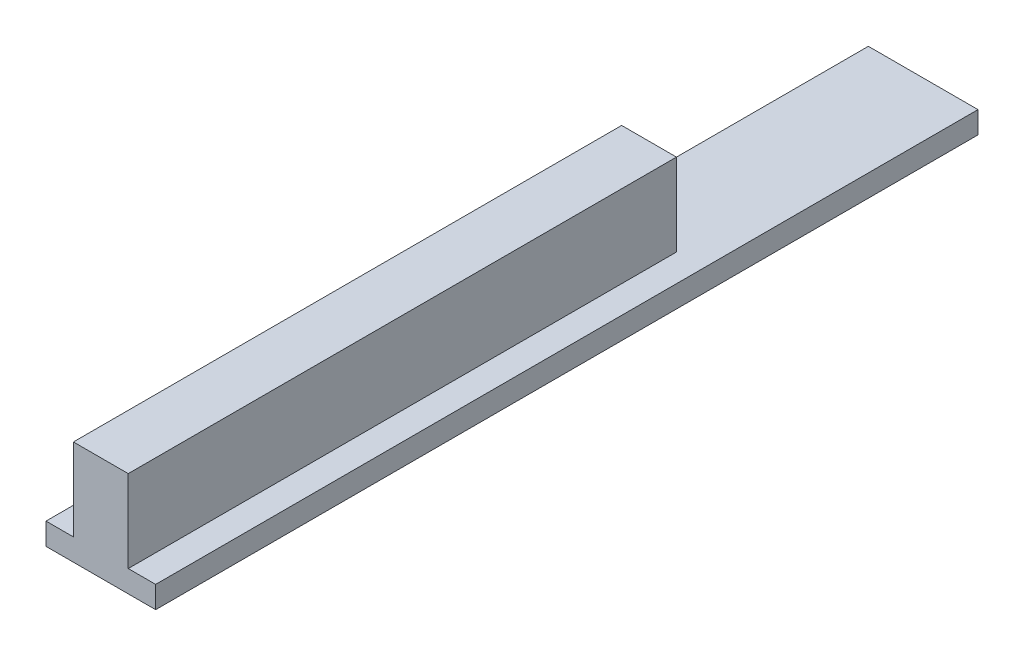
SolidWorks part; units mm, degrees
ref_plane "Front Plane" through (0, 0, 0) normal (0, 0, 1) x (1, 0, 0)
ref_plane "Top Plane" through (0, 0, 0) normal (0, 1, 0) x (1, 0, 0)
ref_plane "Right Plane" through (0, 0, 0) normal (1, 0, 0) x (0, 0, -1)
sketch "Sketch1" plane through (0, 0, 0) normal (0, 0, 1) x (1, 0, 0)
  line L0 (10, 0) -> (-10, 0)
  line L1 (0, 24.7212) -> (0, -43.2343) construction
  line L2 (-41.2644, 0) -> (34.5487, 0) construction
  line L3 (-10, 0) -> (-10, 4)
  line L4 (-10, 4) -> (-5, 4)
  line L5 (-5, 4) -> (-5, 9)
  line L6 (-12.4915, 9) -> (5, 9) construction
  line L7 (5, 19) -> (-5, 19)
  line L8 (10, 4) -> (5, 4)
  line L9 (10, 0) -> (10, 4)
  line L10 (5, 4) -> (5, 9)
  line L11 (-5, 9) -> (-5, 19)
  line L12 (5, 9) -> (5, 19)
  line L13 (5, 4) -> (-5, 4)
  point P0 (-15, 4)
  point P8 (0, 0)
  point P12 (0, -20.5804)
  point P14 (0, -43.2343)
  point P15 (0, -43.2343)
  point P16 (0, -43.2343)
  point P29 (0, 19)
  dimension "D1" = 20
  dimension "D4" = 5
  dimension "D5" = 4
  dimension "D6" = 5
  dimension "D8" = 10
extrude "Boss-Extrude1" add sketch "Sketch1" along normal blind 100 contours L8 L13 L4 L3 L0 L9 | L13 L10 L12 L7 L11 L5 region at (0, 2, 0) region at (0, 11.5, 0)
extrude "Boss-Extrude2" add sketch "Sketch1<3>" against normal blind 50 contours L8 L13 L4 L3 L0 L9 region at (0, 2, 0)
sketch "Sketch1<3>" plane through (0, 0, 0) normal (0, 0, 1) x (1, 0, 0) same geometry as "Sketch1"
